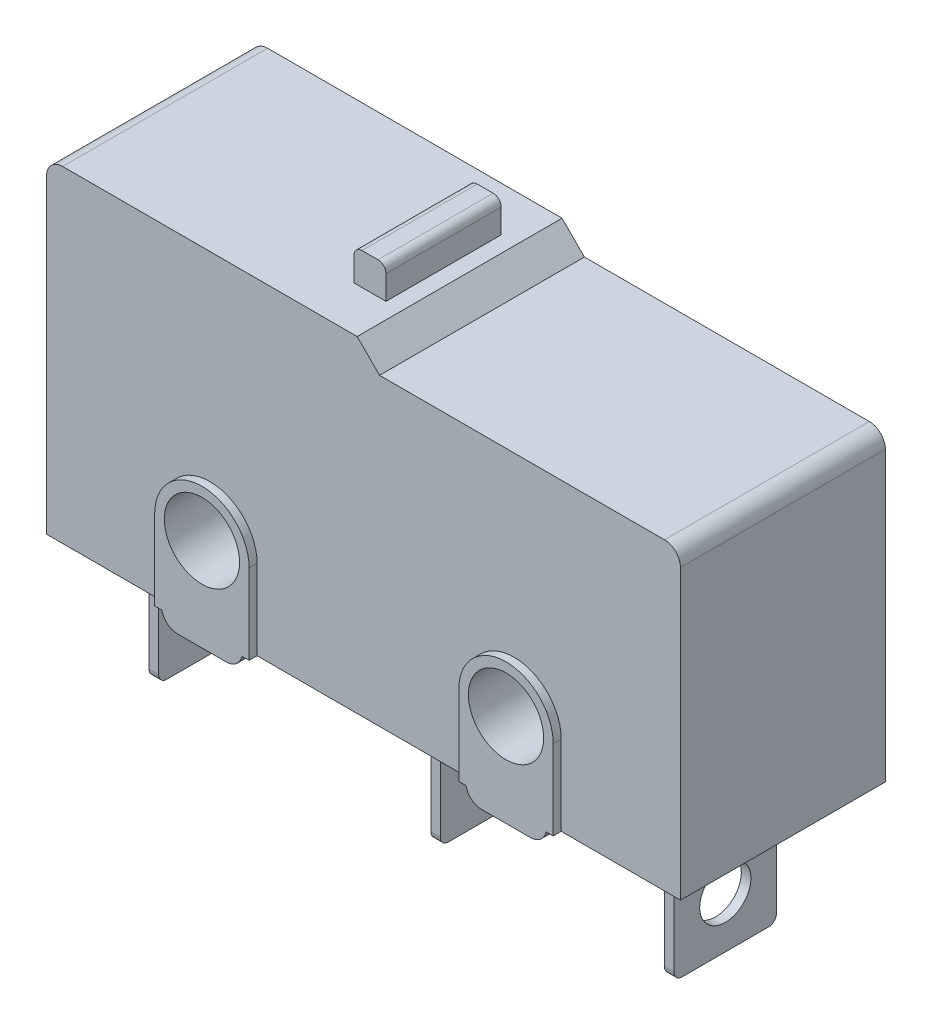
SolidWorks part; units mm, degrees
ref_plane "Front Plane" through (0, 0, 0) normal (0, 0, 1) x (1, 0, 0)
ref_plane "Top Plane" through (0, 0, 0) normal (0, 1, 0) x (1, 0, 0)
ref_plane "Right Plane" through (0, 0, 0) normal (1, 0, 0) x (0, 0, -1)
sketch "Sketch1" plane through (0, 0, 0) normal (0, 0, 1) x (1, 0, 0)
  line L0 (0, 0) -> (-3.95, 0)
  line L1 (-6.45, 0) -> (-6.45, -0.4)
  line L2 (-6.45, -0.4) -> (-3.95, -0.4)
  line L3 (-3.95, -0.4) -> (-3.95, 0)
  line L4 (-6.45, 0) -> (-13.45, 0)
  line L5 (-15.95, 0) -> (-15.95, -0.4)
  line L6 (-15.95, -0.4) -> (-13.45, -0.4)
  line L7 (-13.45, -0.4) -> (-13.45, 0)
  line L9 (-19.8, 0) -> (-19.8, 10.2)
  line L10 (-19.8, 10.2) -> (-10.1, 10.2)
  line L11 (-10.1, 10.2) -> (-9.4, 9.5)
  line L12 (-9.4, 9.5) -> (0, 9.5)
  line L13 (0, 9.5) -> (0, 0)
  line L14 (-14.7, -0.4) -> (-14.7, 2.5) construction
  line L15 (-5.2, -0.4) -> (-5.2, 2.5) construction
  line L16 (-14.7, 2.5) -> (-5.2, 2.5) construction
  line L17 (-15.95, 0) -> (-19.8, 0)
  circle A0 centre (-14.7, 2.5) radius 1.175
  circle A1 centre (-5.2, 2.5) radius 1.175
  dimension "D1" = 2.35
  dimension "D5" = 5.1
  dimension "D2" = 10.2
  dimension "D3" = 9.5
  dimension "D4" = 19.8
  dimension "D6" = 9.5
  dimension "D7" = 2.5
  dimension "D8" = 2.9
  dimension "D9" = 2.5
  dimension "D10" = 10.4
  dimension "D11" = 45
extrude "Boss-Extrude1" add sketch "Sketch1" along normal blind 6.4
sketch "Sketch2" plane through (0, 10.2, 0) normal (0, 1, 0) x (1, 0, 0)
  line L0 (-19.8, -3.2) -> (-10.1, -3.2) construction
  line L1 (-19.8, -6.4) -> (-19.8, 0) construction
  line L2 (-10.1, -6.4) -> (-10.1, 0) construction
  line L4 (-10.6, -5) -> (-11.6, -5)
  line L5 (-10.6, -5) -> (-10.6, -1.4)
  line L6 (-10.6, -1.4) -> (-11.6, -1.4)
  line L7 (-11.6, -5) -> (-11.6, -1.4)
  line L8 (-10.6, -5) -> (-11.6, -1.4) construction
  line L9 (-10.6, -1.4) -> (-11.6, -5) construction
  point P6 (-11.1, -3.2)
  dimension "D1" = 3.6
  dimension "D2" = 1
  dimension "D3" = 0.5
extrude "Boss-Extrude2" add sketch "Sketch2" along normal blind 1
sketch "Sketch3" plane through (0, 0, 0) normal (0, -1, 0) x (1, 0, 0)
  line L0 (-19.8, 3.2) -> (0, 3.2) construction
  line L1 (-19.8, 6.4) -> (-19.8, 0) construction
  line L2 (0, 6.4) -> (0, 0) construction
  line L4 (-17.9, 1.6) -> (-18.2, 1.6)
  line L5 (-17.9, 1.6) -> (-17.9, 4.8)
  line L6 (-17.9, 4.8) -> (-18.2, 4.8)
  line L7 (-18.2, 1.6) -> (-18.2, 4.8)
  line L8 (-17.9, 1.6) -> (-18.2, 4.8) construction
  line L9 (-17.9, 4.8) -> (-18.2, 1.6) construction
  line L10 (-9.1, 1.6) -> (-9.4, 1.6)
  line L11 (-9.1, 1.6) -> (-9.1, 4.8)
  line L12 (-9.1, 4.8) -> (-9.4, 4.8)
  line L13 (-9.4, 1.6) -> (-9.4, 4.8)
  line L14 (-9.1, 1.6) -> (-9.4, 4.8) construction
  line L15 (-9.1, 4.8) -> (-9.4, 1.6) construction
  line L16 (-1.8, 1.6) -> (-2.1, 1.6)
  line L17 (-1.8, 1.6) -> (-1.8, 4.8)
  line L18 (-1.8, 4.8) -> (-2.1, 4.8)
  line L19 (-2.1, 1.6) -> (-2.1, 4.8)
  line L20 (-1.8, 1.6) -> (-2.1, 4.8) construction
  line L21 (-1.8, 4.8) -> (-2.1, 1.6) construction
  point P6 (-18.05, 3.2)
  point P11 (-9.25, 3.2)
  point P16 (-1.95, 3.2)
  dimension "D1" = 3.2
  dimension "D2" = 0.3
  dimension "D3" = 1.6
  dimension "D4" = 8.8
  dimension "D5" = 7.3
extrude "Boss-Extrude3" add sketch "Sketch3" along normal blind 3.9
sketch "Sketch4" plane through (-1.8, 0, 0) normal (1, 0, 0) x (0, 0, -1)
  line L0 (-3.2, 0) -> (-3.2, -3.9) construction
  line L1 (-6.4, 0) -> (0, 0) construction
  line L2 (-1.6, -3.9) -> (-4.8, -3.9) construction
  circle A0 centre (-3.2, -2.3) radius 0.8
  dimension "D1" = 1.6
  dimension "D2" = 1.6
extrude "Cut-Extrude1" cut sketch "Sketch4" against normal through all
sketch "Sketch5" plane through (0, 0, 6.4) normal (0, 0, 1) x (1, 0, 0)
  line L0 (-16.175, 2.5) -> (-16.175, 0)
  line L1 (-19.8, 0) -> (-15.95, 0) construction
  line L2 (-16.175, 0) -> (-15.95, 0)
  line L3 (-15.95, 0) -> (-15.95, -0.4)
  line L4 (-15.95, -0.4) -> (-13.45, -0.4)
  line L5 (-13.45, -0.4) -> (-13.45, 0)
  line L6 (-13.225, 2.5) -> (-13.225, 0)
  line L7 (-13.45, 0) -> (-6.45, 0) construction
  line L8 (-13.225, 0) -> (-13.45, 0)
  line L9 (-6.675, 2.5) -> (-6.675, 0)
  line L10 (-6.675, 0) -> (-6.45, 0)
  line L11 (-6.45, 0) -> (-6.45, -0.4)
  line L12 (-6.45, -0.4) -> (-3.95, -0.4)
  line L13 (-3.95, -0.4) -> (-3.95, 0)
  line L14 (-3.725, 2.5) -> (-3.725, 0)
  line L15 (-3.95, 0) -> (0, 0) construction
  line L16 (-3.725, 0) -> (-3.95, 0)
  circle A9 centre (-14.7, 2.5) radius 1.475
  arc A10 (-13.225, 2.5) -> (-16.175, 2.5) centre (-14.7, 2.5) ccw
  circle A11 centre (-14.7, 2.5) radius 1.175 construction
  circle A12 centre (-5.2, 2.5) radius 1.475
  arc A13 (-3.725, 2.5) -> (-6.675, 2.5) centre (-5.2, 2.5) ccw
  circle A14 centre (-5.2, 2.5) radius 1.175 construction
  circle A15 centre (-14.7, 2.5) radius 1.175
  circle A16 centre (-5.2, 2.5) radius 1.175
  dimension "D1" = 0.3
  dimension "D2" = 0.3
extrude "Boss-Extrude4" add sketch "Sketch5" along normal blind 0.25 and the other way offset from surface (6.65 mm away) 0.25 other way up to face at (-13.525, 2.5, 0)
fillet "Fillet1" radius 0.5 6 edges at (-19.8, 10.2, 3.2) (0, 9.5, 3.2) (-3.95, -0.4, 3.2) (-6.45, -0.4, 3.2) (-13.45, -0.4, 3.2) (-15.95, -0.4, 3.2)
fillet "Fillet2" radius 0.25 6 edges at (-1.95, -3.9, 1.6) (-9.25, -3.9, 1.6) (-18.05, -3.9, 1.6) (-18.05, -3.9, 4.8) (-1.95, -3.9, 4.8) (-9.25, -3.9, 4.8)
fillet "Fillet3" radius 0.25 2 edges at (-11.6, 11.2, 3.2) (-10.6, 11.2, 3.2)
